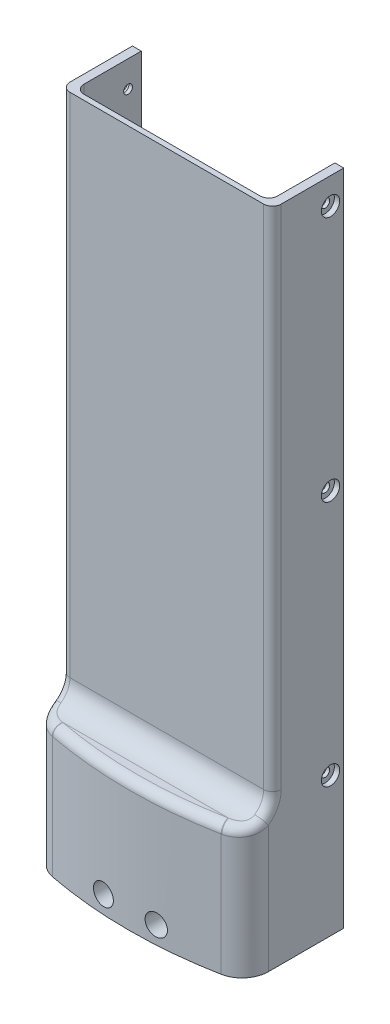
SolidWorks part; units mm, degrees
ref_plane "Front Plane" through (0, 0, 0) normal (0, 0, 1) x (1, 0, 0)
ref_plane "Top Plane" through (0, 0, 0) normal (0, 1, 0) x (1, 0, 0)
ref_plane "Right Plane" through (0, 0, 0) normal (1, 0, 0) x (0, 0, -1)
sketch "Sketch1" plane through (0, 0, 0) normal (0, 0, 1) x (1, 0, 0)
  line L1 (60, -150) -> (-60, -150)
  line L2 (60, -150) -> (60, 150)
  line L3 (60, 150) -> (-60, 150)
  line L4 (-60, -150) -> (-60, 150)
  line L5 (60, -150) -> (-60, 150) construction
  line L6 (60, 150) -> (-60, -150) construction
  point P0 (0, 0)
  dimension "D1" = 120
  dimension "D2" = 300
extrude "Boss-Extrude1" add sketch "Sketch1" along normal blind 3
ref_plane "Plane1" through (0, -224, 0) normal (0, -1, 0) x (-1, 0, 0)
sketch "Sketch2" plane through (0, -224, 0) normal (0, -1, 0) x (-1, 0, 0)
  line L0 (-60, 0) -> (60, 0) construction
  line L1 (-60, 0) -> (-60, -17.3262)
  line L2 (60, 0) -> (60, -17.3262)
  line L3 (60, 0) -> (-60, 0)
  circle A0 centre (0, 230) radius 254.5
  dimension "D2" = 509
  dimension "D1" = 230
extrude "Boss-Extrude2" add sketch "Sketch2" against normal blind 74 contours L1 A0 L2 L3 region at (0, -224, 11.1642)
sketch "Sketch3" plane through (0, 0, 0) normal (0, 0, -1) x (-1, 0, 0)
  line L0 (-55, -224) -> (55, -224) construction
  line L1 (7.5, -234) -> (-7.5, -234)
  line L2 (7.5, -234) -> (7.5, -214)
  line L3 (7.5, -214) -> (-7.5, -214)
  line L4 (-7.5, -234) -> (-7.5, -214)
  line L5 (7.5, -234) -> (-7.5, -214) construction
  line L6 (7.5, -214) -> (-7.5, -234) construction
  point P0 (0, -224)
  dimension "D1" = 15
  dimension "D2" = 20
extrude "Cut-Extrude1" cut sketch "Sketch3" against normal blind 20
fillet "Fillet1" radius 3 2 edges at (-7.5, -219, 20) (7.5, -219, 20)
fillet "Fillet2" radius 15 2 edges at (-60, -187, 17.3262) (60, -187, 17.3262)
fillet "Fillet3" radius 12 1 edges at (0, -150, 3)
sketch "Sketch4" plane through (0, 0, 0) normal (0, 0, -1) x (-1, 0, 0)
  line L0 (-7.5, -224) -> (-60, -224) construction
  line L1 (-60, 150) -> (-55, 150)
  line L2 (-60, 150) -> (-60, -224)
  line L3 (-60, -224) -> (-55, -224)
  line L4 (-55, 150) -> (-55, -224)
  line L5 (0, 13.475) -> (0, -13.475) construction
  line L6 (55, 150) -> (55, -224)
  line L7 (60, -224) -> (55, -224)
  line L8 (60, 150) -> (60, -224)
  line L9 (60, 150) -> (55, 150)
  dimension "D1" = 5
extrude "Boss-Extrude3" add sketch "Sketch4" along normal blind 37.5
fillet "Fillet5" radius 5 9 edges at (60, 6, 3) (60, -141.6615, 3.5723) (58.9444, -149.2267, 10.762) (52.5238, -150, 18.2111) (-60, 6, 3) (-60, -141.6615, 3.5723) (-59.5382, -148.3502, 8.9276) (-52.5238, -150, 18.2111) (0, -150, 24.5)
fillet "Fillet6" radius 5 2 edges at (-55, -37, 0) (55, -37, 0)
sketch "Sketch5" plane through (0, 0, 0) normal (0, 0, -1) x (-1, 0, 0)
  line L0 (0, 13.475) -> (0, -13.475) construction
  line L1 (-7.5, -224) -> (-27.5, -224)
  line L2 (-7.5, -224) -> (-7.5, -204)
  line L3 (-7.5, -204) -> (-27.5, -204)
  line L4 (-27.5, -224) -> (-27.5, -204)
  line L5 (27.5, -224) -> (27.5, -204)
  line L6 (7.5, -204) -> (27.5, -204)
  line L7 (7.5, -224) -> (7.5, -204)
  line L8 (7.5, -224) -> (27.5, -224)
  dimension "D1" = 20
  dimension "D2" = 20
extrude "Boss-Extrude4" add sketch "Sketch5" along normal blind 22.5
sketch "Sketch6" plane through (0, 0, -22.5) normal (0, 0, -1) x (-1, 0, 0)
  line L0 (-7.5, -224) -> (-7.5, -204) construction
  line L1 (-27.5, -224) -> (-7.5, -224) construction
  line L2 (0, 13.475) -> (0, -13.475) construction
  circle A0 centre (-15, -214) radius 2.5
  circle A1 centre (15, -214) radius 2.5
  dimension "D1" = 7.5
  dimension "D2" = 10
extrude "Cut-Extrude2" cut sketch "Sketch6" against normal blind 10
sketch "Sketch7" plane through (0, 0, -12.5) normal (0, 0, -1) x (-1, 0, 0)
  circle A0 centre (-15, -214) radius 6
  circle A1 centre (15, -214) radius 6
extrude "Cut-Extrude3" cut sketch "Sketch7" against normal blind 51
sketch "Sketch8" plane through (-60, 0, 0) normal (-1, 0, 0) x (0, 0, 1)
  line L0 (-37.5, -224) -> (-37.5, 150) construction
  line L1 (-2, 150) -> (-37.5, 150) construction
  circle A0 centre (-30, 135) radius 2.5
  circle A1 centre (-30, -5) radius 2.5
  circle A2 centre (-30, -145) radius 2.5
  dimension "D1" = 7.5
  dimension "D2" = 15
extrude "Cut-Extrude4" cut sketch "Sketch8" against normal blind 5
mirror "Mirror1" about plane through (0, 0, 0) normal (1, 0, 0) of "Cut-Extrude4"
sketch "Sketch9" plane through (-60, 0, 0) normal (-1, 0, 0) x (0, 0, 1)
  circle A0 centre (-30, 135) radius 5.2
  circle A1 centre (-30, -5) radius 5.2
  circle A2 centre (-30, -145) radius 5.2
extrude "Cut-Extrude5" cut sketch "Sketch9" against normal blind 3
mirror "Mirror2" about plane through (0, 0, 0) normal (1, 0, 0) of "Cut-Extrude5"
